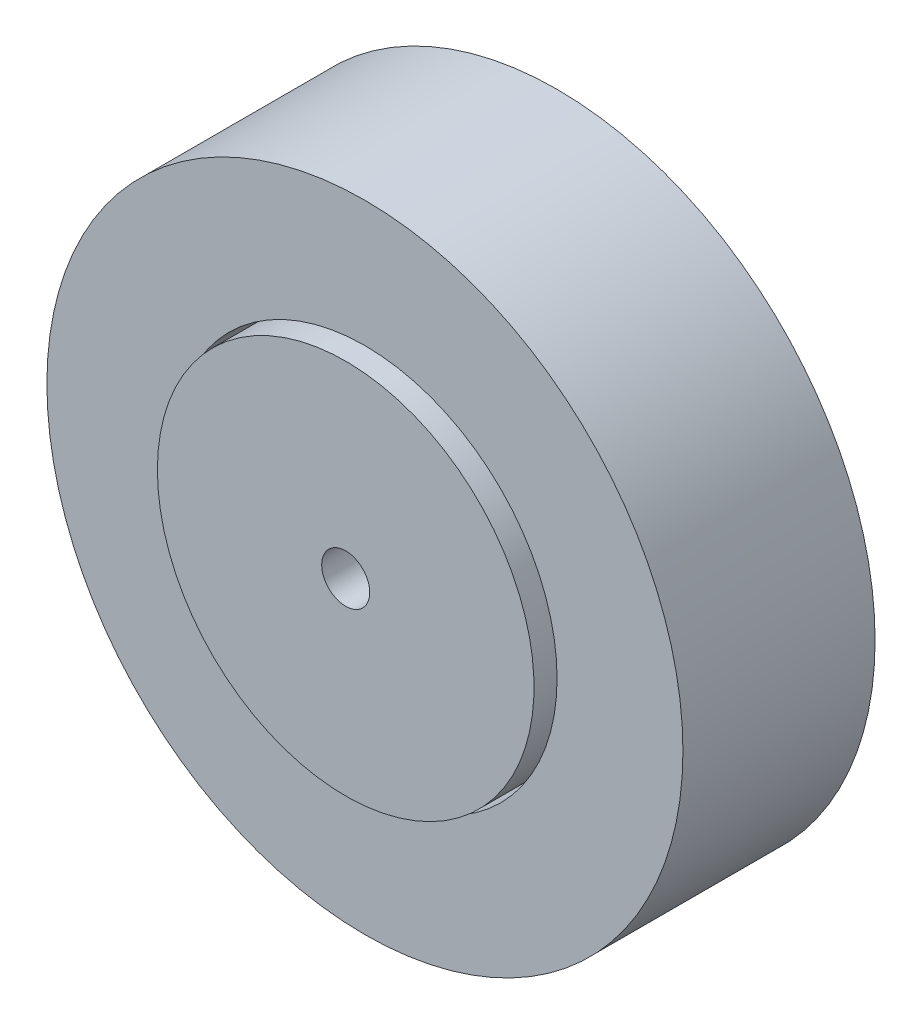
SolidWorks part; units mm, degrees
ref_plane "Front Plane" through (0, 0, 0) normal (0, 0, 1) x (1, 0, 0)
ref_plane "Top Plane" through (0, 0, 0) normal (0, 1, 0) x (1, 0, 0)
ref_plane "Right Plane" through (0, 0, 0) normal (1, 0, 0) x (0, 0, -1)
sketch "Sketch1" plane through (0, 0, 0) normal (0, 0, 1) x (1, 0, 0)
  circle A0 centre (0, 0) radius 1.5875
  circle A1 centre (0, 0) radius 12.446
  dimension "D1" = 3.175
  dimension "D2" = 24.892
extrude "Boss-Extrude1" add sketch "Sketch1" along normal mid plane 15.24
sketch "Sketch2" plane through (0, 0, 0) normal (0, 0, 1) x (1, 0, 0)
  circle A0 centre (0, 0) radius 21.0185
  circle A1 centre (0, 0) radius 12.7
  dimension "D1" = 42.037
extrude "Boss-Extrude2" add sketch "Sketch2" along normal mid plane 12.7
